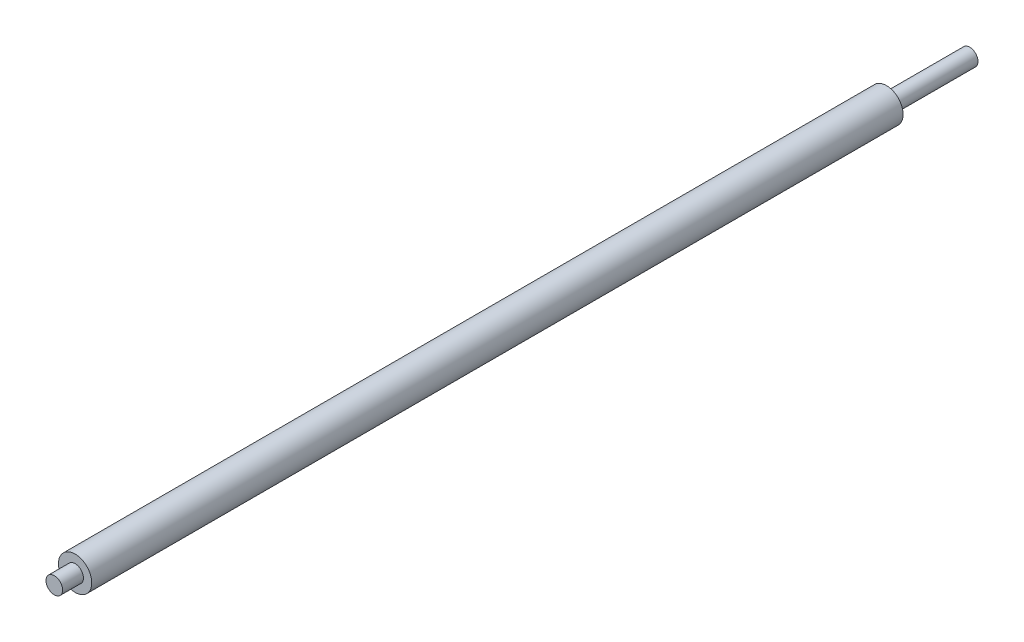
SolidWorks part; units mm, degrees
ref_plane "Front Plane" through (0, 0, 0) normal (0, 0, 1) x (1, 0, 0)
ref_plane "Top Plane" through (0, 0, 0) normal (0, 1, 0) x (1, 0, 0)
ref_plane "Right Plane" through (0, 0, 0) normal (1, 0, 0) x (0, 0, -1)
sketch "Sketch1" plane through (0, 0, 0) normal (0, 0, 1) x (1, 0, 0)
  circle A0 centre (0, 0) radius 6
  dimension "D1" = 12
extrude "Boss-Extrude1" add sketch "Sketch1" along normal mid plane 292.5
sketch "Sketch2" plane through (0, 0, 146.25) normal (0, 0, 1) x (1, 0, 0)
  circle A0 centre (0, 0) radius 3
  dimension "D1" = 6
extrude "Boss-Extrude2" add sketch "Sketch2" along normal blind 7.5
sketch "Sketch3" plane through (0, 0, -146.25) normal (0, 0, -1) x (-1, 0, 0)
  circle A0 centre (0, 0) radius 3
  dimension "D1" = 6
extrude "Boss-Extrude3" add sketch "Sketch3" along normal blind 30
